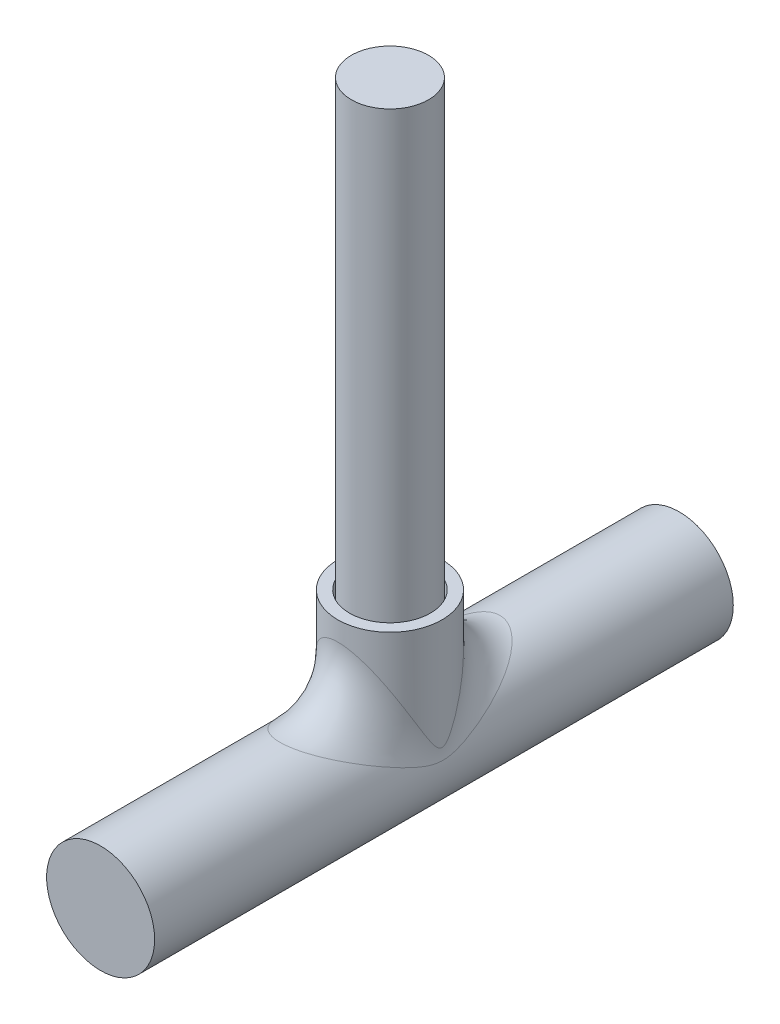
SolidWorks part; units mm, degrees
ref_plane "Front Plane" through (0, 0, 0) normal (0, 0, 1) x (1, 0, 0)
ref_plane "Top Plane" through (0, 0, 0) normal (0, 1, 0) x (1, 0, 0)
ref_plane "Right Plane" through (0, 0, 0) normal (1, 0, 0) x (0, 0, -1)
sketch "Sketch1" plane through (0, 0, 0) normal (0, 0, 1) x (1, 0, 0)
  line L0 (0, 0) -> (0, 14) construction
  circle A0 centre (0, 0) radius 14
  dimension "D1" = 28
extrude "Boss-Extrude1" add sketch "Sketch1" along normal mid plane 150
sketch "Sketch4" plane through (0, 0, -75) normal (0, 0, -1) x (-1, 0, 0)
  line L0 (0, 0) -> (0, 14) construction
  circle A0 centre (0, 0) radius 14 construction
ref_plane "Plane1" through (0, 14, 0) normal (0, 1, 0) x (1, 0, 0)
sketch "Sketch2" plane through (0, 14, 0) normal (0, 1, 0) x (1, 0, 0)
  circle A2 centre (0, 0) radius 13.5
  dimension "D1" = 27
extrude "Boss-Extrude3" add sketch "Sketch2" along normal blind 20 and the other way up to body separate body
fillet "Fillet1" radius 15 1 edges at (1.1285, 13.9544, 13.4528)
sketch "Sketch5" plane through (0, 34, 0) normal (0, 1, 0) x (1, 0, 0)
  circle A0 centre (0, 0) radius 10.5
  dimension "D1" = 21
extrude "Cut-Extrude1" cut sketch "Sketch5" against normal blind 35
sketch "Sketch6" plane through (0, -1, 0) normal (0, 1, 0) x (1, 0, 0)
  circle A0 centre (0, 0) radius 10
  dimension "D1" = 20
extrude "TIL ASSEMBLY - SLETT" add sketch "Sketch6" along normal blind 150
